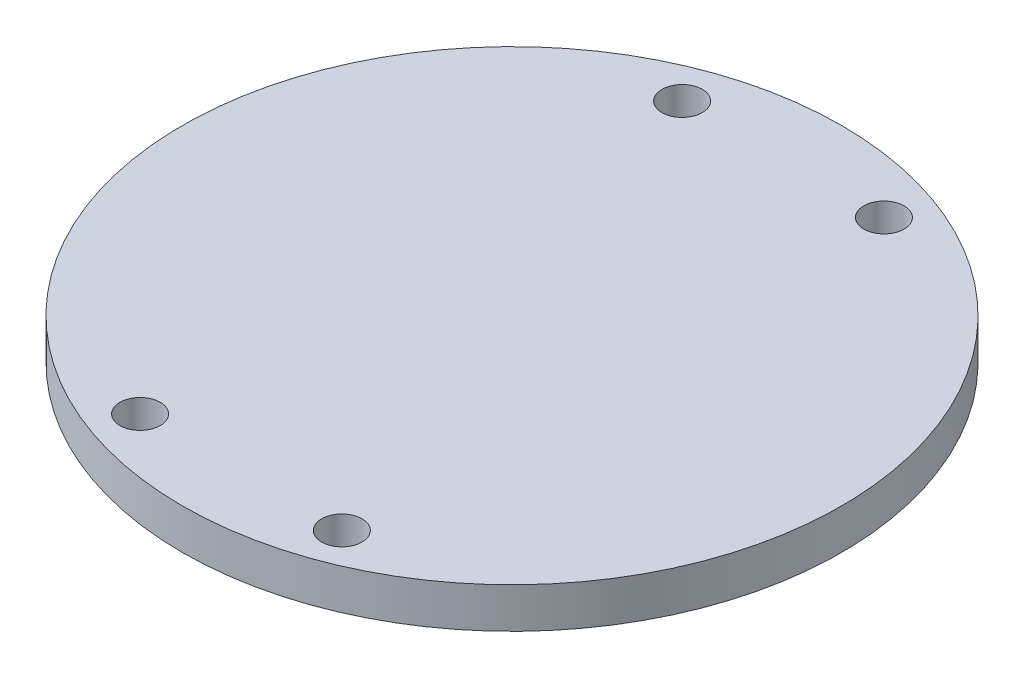
SolidWorks part; units mm, degrees
ref_plane "Front Plane" through (0, 0, 0) normal (0, 0, 1) x (1, 0, 0)
ref_plane "Top Plane" through (0, 0, 0) normal (0, 1, 0) x (1, 0, 0)
ref_plane "Right Plane" through (0, 0, 0) normal (1, 0, 0) x (0, 0, -1)
sketch "Sketch1" plane through (0, 0, 0) normal (0, 1, 0) x (1, 0, 0)
  circle A0 centre (0, 0) radius 49
  dimension "D1" = 98
extrude "Boss-Extrude1" add sketch "Sketch1" along normal blind 6
sketch "Sketch2" plane through (0, 6, 0) normal (0, 1, 0) x (1, 0, 0)
  circle A1 centre (-15, 40.2989) radius 3
  circle A2 centre (15, 40.2989) radius 3
  circle A3 centre (-15, -40.2989) radius 3
  circle A4 centre (15, -40.2989) radius 3
  arc A5 (-17.7733, 39.1549) -> (-17.7733, -39.1549) centre (0, 0) ccw
  arc A6 (12.1537, 41.2467) -> (-12.1537, 41.2467) centre (0, 0) ccw
  arc A7 (17.7733, -39.1549) -> (17.7733, 39.1549) centre (0, 0) ccw
  arc A8 (-12.1537, -41.2467) -> (12.1537, -41.2467) centre (0, 0) ccw
  dimension "D2" = 6
  dimension "D3" = 6
  dimension "D4" = 6
  dimension "D5" = 6
  dimension "D6" = 86
  dimension "D7" = 30
  dimension "D8" = 30
  dimension "D9" = 15
  dimension "D10" = 15
extrude "Cut-Extrude2" cut sketch "Sketch2" against normal blind 6 contours A1 | A2 | A4 | A3 A5 region at (-15, 6, -40.2989) region at (15, 6, -40.2989) region at (-15, 6, 40.2989) region at (15, 6, 40.2989)
